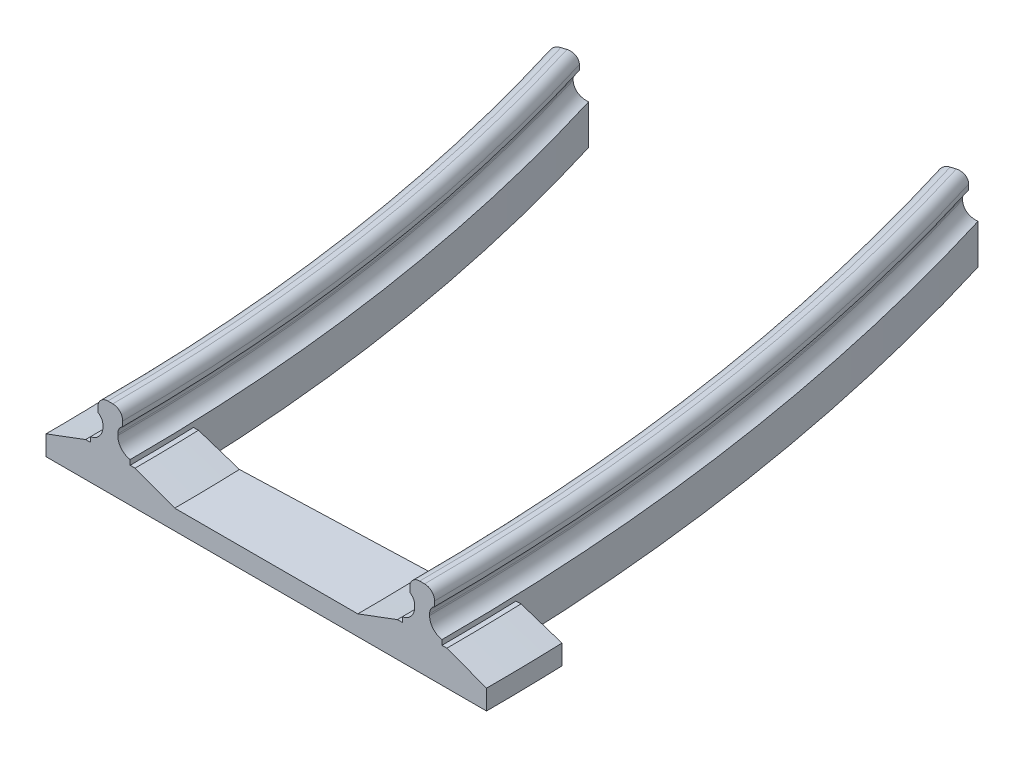
SolidWorks part; units mm, degrees
other "标注1"
sketch "草图3" plane through (-22.25, 4, -10) normal (-0.231, 0.6469, -0.7268) x (-0.9696, -0.2151, 0.1167)
other "标注2"
sketch "草图4" plane through (22.25, 8, -30) normal (0.0083, 0.0567, -0.9984) x (-0.9991, 0.0415, -0.0059)
ref_plane "前视基准面" through (0, 0, 0) normal (0, 0, 1) x (1, 0, 0)
ref_plane "上视基准面" through (0, 0, 0) normal (0, 1, 0) x (1, 0, 0)
ref_plane "右视基准面" through (0, 0, 0) normal (1, 0, 0) x (0, 0, -1)
other "Configuration Table"
sketch "草图1" plane through (0, 0, 0) normal (0, 1, 0) x (1, 0, 0)
  line L0 (-13.75, 14.5) -> (-13.75, -14.5)
  line L13 (-17.75, -14.5) -> (17.75, -14.5)
  line L21 (-17.75, -14.5) -> (-17.75, 14.5)
  line L22 (-17.75, 14.5) -> (17.75, 14.5)
  line L23 (17.75, -14.5) -> (17.75, 14.5)
  line L24 (-17.75, -14.5) -> (17.75, 14.5) construction
  line L25 (-17.75, 14.5) -> (17.75, -14.5) construction
  line L27 (13.75, 14.5) -> (13.75, -14.5)
  line L29 (-13.75, 0) -> (13.75, 0) construction
  line L32 (-22.25, 14.5) -> (22.25, 14.5)
  line L33 (-22.25, 14.5) -> (-22.25, 6.5)
  line L34 (-22.25, 6.5) -> (22.25, 6.5)
  line L35 (22.25, 14.5) -> (22.25, 6.5)
  point P0 (0, 0)
  point P15 (0, 6.5)
  dimension "D3" = 27.5
  dimension "D4" = 8
  dimension "D1" = 35.5
  dimension "D2" = 29
  dimension "D5" = 44.5
extrude "凸台-拉伸1" add sketch "草图1" along normal blind 4 contours L34 L21 L13 L0 | L34 L27 L13 L23 | L27 L34 L23 L22 | L21 L34 L0 L22 region at (-15.75, 0, -10.5) region at (-15.75, 0, 4) region at (15.75, 0, -10.5) region at (15.75, 0, 4)
extrude "凸台-拉伸2" add sketch "草图1<7>" along normal blind 3.5 contours L34 L35 L32 L33
sketch "草图1<7>" plane through (0, 0, 0) normal (0, 1, 0) x (1, 0, 0) same geometry as "草图1"
sketch "草图2" plane through (0, 0, -14.5) normal (0, 0, -1) x (-1, 0, 0)
  line L0 (18.25, 3.5) -> (22.25, 2)
  line L1 (22.25, 3.5) -> (18.25, 3.5)
  line L2 (22.25, 3.5) -> (22.25, 2)
  line L3 (22.25, 2) -> (18.25, 2) construction
  line L4 (18.25, 3.5) -> (18.25, 2) construction
  line L5 (-22.25, 2) -> (-18.25, 3.5)
  line L6 (-22.25, 3.5) -> (-18.25, 3.5)
  line L7 (-22.25, 3.5) -> (-22.25, 2)
  line L8 (-22.25, 2) -> (-18.25, 2) construction
  line L9 (-18.25, 3.5) -> (-18.25, 2) construction
  line L10 (13.75, 3.5) -> (-13.75, 3.5) construction
  line L11 (-13.25, 3.5) -> (-9.25, 3.5)
  line L12 (-13.25, 3.5) -> (-13.25, 2) construction
  line L13 (-13.25, 2) -> (-9.25, 2) construction
  line L14 (-9.25, 3.5) -> (-9.25, 2)
  line L15 (-13.75, 3.5) -> (-13.25, 3.5) construction
  line L16 (13.25, 3.5) -> (9.25, 3.5)
  line L17 (13.25, 3.5) -> (13.25, 2) construction
  line L18 (13.25, 2) -> (9.25, 2) construction
  line L19 (9.25, 3.5) -> (9.25, 2)
  line L20 (13.25, 3.5) -> (13.75, 3.5) construction
  line L21 (17.75, 3.5) -> (18.25, 3.5) construction
  line L22 (-13.25, 3.5) -> (-9.25, 2)
  line L23 (9.25, 2) -> (13.25, 3.5)
  line L24 (-9.25, 2) -> (9.25, 2)
  line L25 (-9.25, 3.5) -> (9.25, 3.5)
  line L26 (-15.75, 4) -> (-15.75, 6.5) construction
  line L27 (14.5, 8) -> (17, 8)
  line L28 (14.5, 8) -> (14.5, 6.5)
  line L29 (14.5, 6.5) -> (17, 6.5)
  line L30 (17, 8) -> (17, 6.5)
  line L31 (-17, 8) -> (-14.5, 8)
  line L32 (-17, 8) -> (-17, 6.5)
  line L33 (-17, 6.5) -> (-14.5, 6.5)
  line L34 (-14.5, 8) -> (-14.5, 6.5)
  line L35 (-13.75, 4) -> (-17.75, 4) construction
  line L36 (15.75, 6.5) -> (15.75, 4) construction
  line L37 (17.75, 4) -> (13.75, 4) construction
  line L38 (15, 6.5) -> (15, 4)
  line L39 (16.5, 6.5) -> (16.5, 4)
  line L40 (16.5, 4) -> (15.75, 4)
  line L41 (15.75, 4) -> (15, 4)
  line L42 (-16.5, 6.5) -> (-16.5, 4)
  line L43 (-16.5, 4) -> (-15.75, 4)
  line L44 (-15.75, 4) -> (-15, 4)
  line L45 (-15, 4) -> (-15, 6.5)
  line M9 (22.25, 3.5) -> (17.75, 3.5)
  line M11 (17.75, 4) -> (13.75, 4)
  line M13 (13.75, 3.5) -> (-13.75, 3.5)
  line M15 (-13.75, 4) -> (-17.75, 4)
  line M17 (-17.75, 3.5) -> (-22.25, 3.5)
  line M18 (-22.25, 3.5) -> (-22.25, 0)
  line M20 (22.25, 0) -> (22.25, 3.5)
  dimension "D1" = 4
  dimension "D2" = 1.5
  dimension "D3" = 2.5
  dimension "D4" = 1.5
  dimension "D5" = 2.5
  dimension "D6" = 1.5
extrude "切除-拉伸1" cut sketch "草图2" against normal through all contours L14 L24 L19 M13 | L19 L23 M13 | L22 L14 M13 | L5 M18 M17 | L0 M9 M20 region at (-20.9167, 3, -14.5) region at (20.9167, 3, -14.5) region at (10.5833, 3, -14.5) region at (0, 2.75, -14.5) region at (-10.5833, 3, -14.5)
extrude "凸台-拉伸4" add sketch "草图2<3>" against normal through all contours L34 L31 L32 L33 | L45 L33 L42 M15 | L30 L27 L28 L29 | L39 L29 L38 M11 region at (-15.75, 7.25, -14.5) region at (-15.75, 5.25, -14.5) region at (15.75, 7.25, -14.5) region at (15.75, 5.25, -14.5)
sketch "草图2<3>" plane through (0, 0, -14.5) normal (0, 0, -1) x (-1, 0, 0) same geometry as "草图2"
fillet "圆角1" radius 1 4 edges at (-16.5, 6.5, 0) (-15, 6.5, 0) (15, 6.5, 0) (16.5, 6.5, 0)
fillet "圆角2" radius 1.5 4 edges at (16.5, 4, 0) (15, 4, 0) (-15, 4, 0) (-16.5, 4, 0)
fillet "圆角3" radius 1 4 edges at (-17, 8, 0) (14.5, 8, 0) (17, 8, 0) (-14.5, 8, 0)
sketch "草图5" plane through (0, 0, -14.5) normal (0, 0, -1) x (-1, 0, 0)
  line L26 (17, 6.5) -> (17, 7)
  line L27 (16, 8) -> (15.5, 8)
  line L28 (14.5, 7) -> (14.5, 6.5)
  line L29 (15, 5.634) -> (15, 5.479)
  line L30 (13.75, 4) -> (13.75, 3.5)
  line L31 (13.75, 3.5) -> (13.25, 3.5)
  line L32 (13.25, 3.5) -> (9.25, 2)
  line L33 (9.25, 2) -> (-9.25, 2)
  line L34 (-9.25, 2) -> (-13.25, 3.5)
  line L35 (-13.25, 3.5) -> (-13.75, 3.5)
  line L36 (-13.75, 3.5) -> (-13.75, 4)
  line L37 (-15, 5.479) -> (-15, 5.634)
  line L38 (-14.5, 6.5) -> (-14.5, 7)
  line L39 (-15.5, 8) -> (-16, 8)
  line L40 (-17, 7) -> (-17, 6.5)
  line L41 (-16.5, 5.634) -> (-16.5, 5.479)
  line L42 (-17.75, 4) -> (-17.75, 3.5)
  line L43 (-17.75, 3.5) -> (-18.25, 3.5)
  line L44 (-18.25, 3.5) -> (-22.25, 2)
  line L45 (-22.25, 2) -> (-22.25, 0)
  line L46 (-22.25, 0) -> (22.25, 0)
  line L47 (22.25, 0) -> (22.25, 2)
  line L48 (22.25, 2) -> (18.25, 3.5)
  line L49 (18.25, 3.5) -> (17.75, 3.5)
  line L50 (17.75, 3.5) -> (17.75, 4)
  line L51 (16.5, 5.479) -> (16.5, 5.634)
  line L52 (17, 6.5) -> (17, 7)
  line L53 (16, 8) -> (15.5, 8)
  line L54 (14.5, 7) -> (14.5, 6.5)
  line L55 (15, 5.634) -> (15, 5.479)
  line L56 (13.75, 4) -> (13.75, 3.5)
  line L57 (13.75, 3.5) -> (13.25, 3.5)
  line L58 (13.25, 3.5) -> (9.25, 2)
  line L59 (9.25, 2) -> (-9.25, 2)
  line L60 (-9.25, 2) -> (-13.25, 3.5)
  line L61 (-13.25, 3.5) -> (-13.75, 3.5)
  line L62 (-13.75, 3.5) -> (-13.75, 4)
  line L63 (-15, 5.479) -> (-15, 5.634)
  line L64 (-14.5, 6.5) -> (-14.5, 7)
  line L65 (-15.5, 8) -> (-16, 8)
  line L66 (-17, 7) -> (-17, 6.5)
  line L67 (-16.5, 5.634) -> (-16.5, 5.479)
  line L68 (-17.75, 4) -> (-17.75, 3.5)
  line L69 (-17.75, 3.5) -> (-18.25, 3.5)
  line L70 (-18.25, 3.5) -> (-22.25, 2)
  line L71 (-22.25, 2) -> (-22.25, 0)
  line L72 (-22.25, 0) -> (22.25, 0)
  line L73 (22.25, 0) -> (22.25, 2)
  line L74 (22.25, 2) -> (18.25, 3.5)
  line L75 (18.25, 3.5) -> (17.75, 3.5)
  line L76 (17.75, 3.5) -> (17.75, 4)
  line L77 (16.5, 5.479) -> (16.5, 5.634)
  arc A12 (17, 7) -> (16, 8) centre (16, 7) ccw
  arc A13 (15.5, 8) -> (14.5, 7) centre (15.5, 7) ccw
  arc A14 (15, 5.634) -> (14.5, 6.5) centre (14, 5.634) ccw
  arc A15 (13.75, 4) -> (15, 5.479) centre (13.5, 5.479) ccw
  arc A16 (-15, 5.479) -> (-13.75, 4) centre (-13.5, 5.479) ccw
  arc A17 (-14.5, 6.5) -> (-15, 5.634) centre (-14, 5.634) ccw
  arc A18 (-14.5, 7) -> (-15.5, 8) centre (-15.5, 7) ccw
  arc A19 (-16, 8) -> (-17, 7) centre (-16, 7) ccw
  arc A20 (-16.5, 5.634) -> (-17, 6.5) centre (-17.5, 5.634) ccw
  arc A21 (-17.75, 4) -> (-16.5, 5.479) centre (-18, 5.479) ccw
  arc A22 (16.5, 5.479) -> (17.75, 4) centre (18, 5.479) ccw
  arc A23 (17, 6.5) -> (16.5, 5.634) centre (17.5, 5.634) ccw
  arc A24 (17, 7) -> (16, 8) centre (16, 7) ccw
  arc A25 (15.5, 8) -> (14.5, 7) centre (15.5, 7) ccw
  arc A26 (15, 5.634) -> (14.5, 6.5) centre (14, 5.634) ccw
  arc A27 (13.75, 4) -> (15, 5.479) centre (13.5, 5.479) ccw
  arc A28 (-15, 5.479) -> (-13.75, 4) centre (-13.5, 5.479) ccw
  arc A29 (-14.5, 6.5) -> (-15, 5.634) centre (-14, 5.634) ccw
  arc A30 (-14.5, 7) -> (-15.5, 8) centre (-15.5, 7) ccw
  arc A31 (-16, 8) -> (-17, 7) centre (-16, 7) ccw
  arc A32 (-16.5, 5.634) -> (-17, 6.5) centre (-17.5, 5.634) ccw
  arc A33 (-17.75, 4) -> (-16.5, 5.479) centre (-18, 5.479) ccw
  arc A34 (16.5, 5.479) -> (17.75, 4) centre (18, 5.479) ccw
  arc A35 (17, 6.5) -> (16.5, 5.634) centre (17.5, 5.634) ccw
  dimension "D1" = 0
sketch "草图7" plane through (0, 0, -14.5) normal (0, 0, -1) x (-1, 0, 0)
  line L0 (-17.75, 3.5) -> (-17.75, 0)
  line L1 (-13.75, 3.5) -> (-13.75, 0)
  line L2 (13.75, 3.5) -> (13.75, 0)
  line L3 (17.75, 3.5) -> (17.75, 0)
  line L4 (13.75, 0) -> (17.75, 0)
  line L26 (17, 6.5) -> (17, 7)
  line L27 (16, 8) -> (15.5, 8)
  line L28 (14.5, 7) -> (14.5, 6.5)
  line L29 (15, 5.634) -> (15, 5.479)
  line L30 (13.75, 4) -> (13.75, 3.5)
  line L31 (13.75, 3.5) -> (13.25, 3.5)
  line L32 (13.25, 3.5) -> (9.25, 2)
  line L33 (9.25, 2) -> (-9.25, 2)
  line L34 (-9.25, 2) -> (-13.25, 3.5)
  line L35 (-13.25, 3.5) -> (-13.75, 3.5)
  line L36 (-13.75, 3.5) -> (-13.75, 4)
  line L37 (-15, 5.479) -> (-15, 5.634)
  line L38 (-14.5, 6.5) -> (-14.5, 7)
  line L39 (-15.5, 8) -> (-16, 8)
  line L40 (-17, 7) -> (-17, 6.5)
  line L41 (-16.5, 5.634) -> (-16.5, 5.479)
  line L42 (-17.75, 4) -> (-17.75, 3.5)
  line L43 (-17.75, 3.5) -> (-18.25, 3.5)
  line L44 (-18.25, 3.5) -> (-22.25, 2)
  line L45 (-22.25, 2) -> (-22.25, 0)
  line L46 (-22.25, 0) -> (22.25, 0)
  line L47 (22.25, 0) -> (22.25, 2)
  line L48 (22.25, 2) -> (18.25, 3.5)
  line L49 (18.25, 3.5) -> (17.75, 3.5)
  line L50 (17.75, 3.5) -> (17.75, 4)
  line L51 (16.5, 5.479) -> (16.5, 5.634)
  line L52 (17, 6.5) -> (17, 7)
  line L53 (16, 8) -> (15.5, 8)
  line L54 (14.5, 7) -> (14.5, 6.5)
  line L55 (15, 5.634) -> (15, 5.479)
  line L56 (13.75, 4) -> (13.75, 3.5)
  line L62 (-13.75, 3.5) -> (-13.75, 4)
  line L63 (-15, 5.479) -> (-15, 5.634)
  line L64 (-14.5, 6.5) -> (-14.5, 7)
  line L65 (-15.5, 8) -> (-16, 8)
  line L66 (-17, 7) -> (-17, 6.5)
  line L67 (-16.5, 5.634) -> (-16.5, 5.479)
  line L68 (-17.75, 4) -> (-17.75, 3.5)
  line L72 (-17.75, 0) -> (-13.75, 0)
  line L76 (17.75, 3.5) -> (17.75, 4)
  line L77 (16.5, 5.479) -> (16.5, 5.634)
  arc A12 (17, 7) -> (16, 8) centre (16, 7) ccw
  arc A13 (15.5, 8) -> (14.5, 7) centre (15.5, 7) ccw
  arc A14 (15, 5.634) -> (14.5, 6.5) centre (14, 5.634) ccw
  arc A15 (13.75, 4) -> (15, 5.479) centre (13.5, 5.479) ccw
  arc A16 (-15, 5.479) -> (-13.75, 4) centre (-13.5, 5.479) ccw
  arc A17 (-14.5, 6.5) -> (-15, 5.634) centre (-14, 5.634) ccw
  arc A18 (-14.5, 7) -> (-15.5, 8) centre (-15.5, 7) ccw
  arc A19 (-16, 8) -> (-17, 7) centre (-16, 7) ccw
  arc A20 (-16.5, 5.634) -> (-17, 6.5) centre (-17.5, 5.634) ccw
  arc A21 (-17.75, 4) -> (-16.5, 5.479) centre (-18, 5.479) ccw
  arc A22 (16.5, 5.479) -> (17.75, 4) centre (18, 5.479) ccw
  arc A23 (17, 6.5) -> (16.5, 5.634) centre (17.5, 5.634) ccw
  arc A24 (17, 7) -> (16, 8) centre (16, 7) ccw
  arc A25 (15.5, 8) -> (14.5, 7) centre (15.5, 7) ccw
  arc A26 (15, 5.634) -> (14.5, 6.5) centre (14, 5.634) ccw
  arc A27 (13.75, 4) -> (15, 5.479) centre (13.5, 5.479) ccw
  arc A28 (-15, 5.479) -> (-13.75, 4) centre (-13.5, 5.479) ccw
  arc A29 (-14.5, 6.5) -> (-15, 5.634) centre (-14, 5.634) ccw
  arc A30 (-14.5, 7) -> (-15.5, 8) centre (-15.5, 7) ccw
  arc A31 (-16, 8) -> (-17, 7) centre (-16, 7) ccw
  arc A32 (-16.5, 5.634) -> (-17, 6.5) centre (-17.5, 5.634) ccw
  arc A33 (-17.75, 4) -> (-16.5, 5.479) centre (-18, 5.479) ccw
  arc A34 (16.5, 5.479) -> (17.75, 4) centre (18, 5.479) ccw
  arc A35 (17, 6.5) -> (16.5, 5.634) centre (17.5, 5.634) ccw
  dimension "D1" = 0
sketch "草图6" plane through (0, 0, -14.5) normal (0, 0, -1) x (-1, 0, 0)
  line L0 (0, 0) -> (200, 0) construction
  line L1 (200, 10) -> (200, -10)
  dimension "D1" = 200
  dimension "D2" = 20
revolve "旋转2" add sketch "草图7" angle 17 about L1 reverse direction yes
extrude "切除-拉伸5" cut sketch "草图5<2>" against normal through all
sketch "草图5<2>" plane through (0, 0, -14.5) normal (0, 0, -1) x (-1, 0, 0) same geometry as "草图5"
revolve "旋转1" add sketch "草图5" angle 2 about L1 reverse direction yes
sketch "草图9" plane through (0, 2, 0) normal (0, 1, 0) x (1, 0, 0)
  line L0 (-0.1218, 21.4799) -> (0, 14.5)
  line L1 (-9.3662, 21.1571) -> (9.1225, 21.8027) construction
  line L2 (-9.25, 14.5) -> (9.25, 14.5) construction
